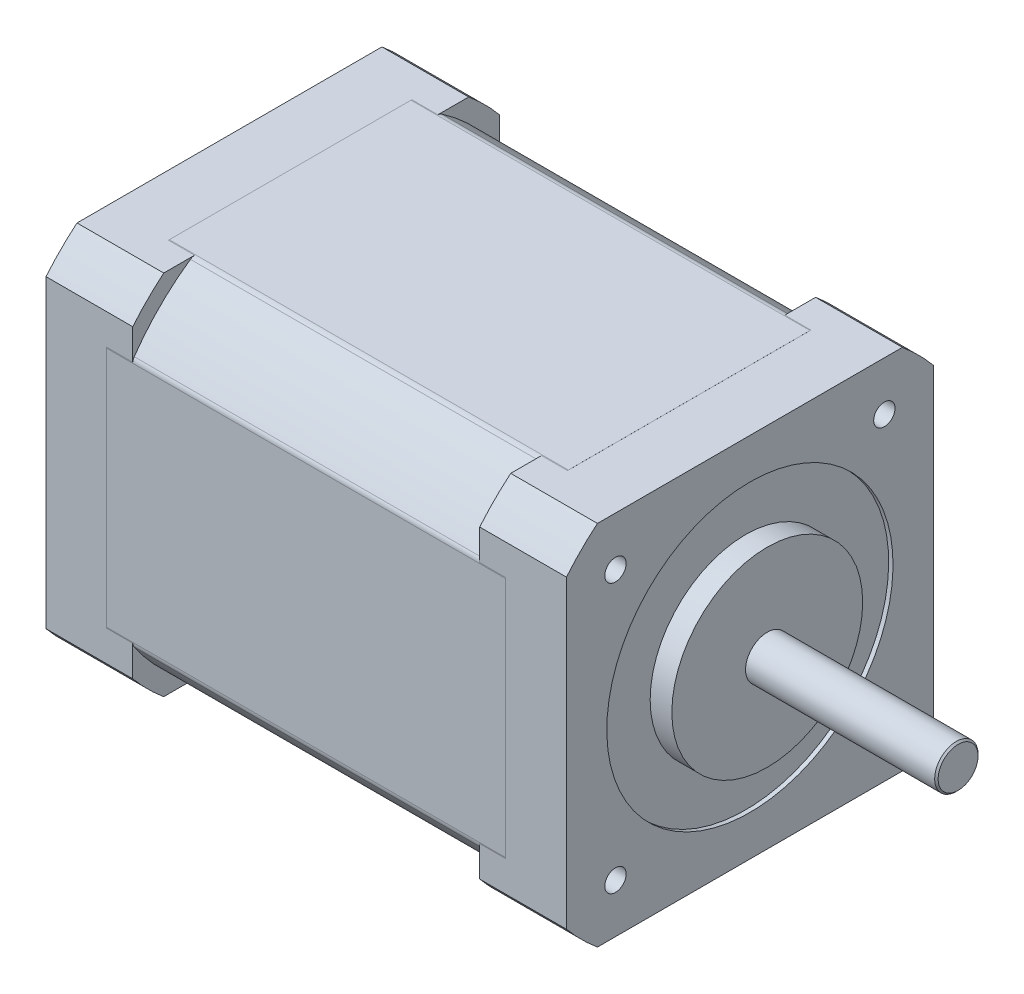
SolidWorks part; units mm, degrees
note: '?' marks a value the reader was unsure of.
ref_plane "Front Plane" through (0, 0, 0) normal (0, 0, 1) x (1, 0, 0)
ref_plane "Top Plane" through (0, 0, 0) normal (0, 1, 0) x (1, 0, 0)
ref_plane "Right Plane" through (0, 0, 0) normal (1, 0, 0) x (0, 0, -1)
ref_axis "Axis_X" through (-52.65, 0, 0) along (1, 0, 0)
ref_axis "Axis_Y" through (0, 24.8602, 0) along (0, -1, 0)?
ref_axis "Axis_Z" through (0, 0, -23.2705) along (0, 0, 1)?
sketch "Sketch1" plane through (0, 0, 0) normal (1, 0, 0) x (0, 0, -1)
  line L1 (-17.5763, 21.15) -> (17.5763, 21.15)
  line L2 (-21.15, 17.5763) -> (-21.15, -17.5763)
  line L3 (-17.5763, -21.15) -> (17.5763, -21.15)
  line L4 (21.15, 17.5763) -> (21.15, -17.5763)
  arc A0 (-17.5763, 21.15) -> (-21.15, 17.5763) centre (0, 0) ccw
  arc A1 (21.15, 17.5763) -> (17.5763, 21.15) centre (0, 0) ccw
  arc A2 (17.5763, -21.15) -> (21.15, -17.5763) centre (0, 0) ccw
  arc A3 (-21.15, -17.5763) -> (-17.5763, -21.15) centre (0, 0) ccw
  dimension "FIX_2" = 55
  dimension "FIX_1" = 42.3
extrude "Boss-Extrude1" add sketch "Sketch1" against normal blind 60
sketch "Sketch2" plane through (0, 0, 0) normal (0, 0, 1) x (1, 0, 0)
  line L0 (0, 0) -> (24, 0) construction
  line L1 (23.8, 2.5) -> (24, 2.3)
  line L2 (0, 0) -> (24, 0)
  line L3 (0, 0) -> (0, 11)
  line L4 (0, 11) -> (2, 11)
  line L5 (2, 2.5) -> (2, 11)
  line L6 (2, 2.5) -> (23.8, 2.5)
  line L9 (24, 2.3) -> (24, 0)
  dimension "FIX_3" = 22
  dimension "FIX_4" = 5
  dimension "FIX_5" = 2
  dimension "FIX_6" = 24
  dimension "FIX_7" = 45
  dimension "FIX_8" = 0.2
revolve "Revolve1" add sketch "Sketch2" angle 360 about axis through (-52.65, 0, 0) along (1, 0, 0)
ref_plane "Plane1" through (-7, 0, 0) normal (1, 0, 0) x (0, 0, -1)
ref_plane "Plane2" through (-53, 0, 0) normal (-1, 0, 0) x (0, 0, 1)
sketch "Sketch3" plane through (0, 21.15, 0) normal (0, 1, 0) x (1, 0, 0)
  line L1 (-50, 21.15) -> (-10, 21.15)
  line L2 (-50, 21.15) -> (-50, -21.15)
  line L3 (-50, -21.15) -> (-10, -21.15)
  line L4 (-10, 21.15) -> (-10, -21.15)
  line L6 (-50, 0) -> (-10, 0) construction
  line L8 (0, 17.5763) -> (0, -17.5763) construction
  line L9 (-60, 0) -> (0, 0) construction
  line L10 (-60, 17.5763) -> (-60, -17.5763) construction
  line L11 (0, -11) -> (0, 11) construction
  point P6 (-30, 0)
  dimension "FIX_12" = 42.3
  dimension "FIX_13" = 10
extrude "Cut-Extrude1" cut sketch "Sketch3" against normal through all
sketch "Sketch4" plane through (-7, 0, 0) normal (1, 0, 0) x (0, 0, -1)
  line L1 (13.9293, -21.155) -> (-13.9293, -21.155)
  line L2 (21.155, -13.9293) -> (21.155, 13.9293)
  line L3 (13.9293, 21.155) -> (-13.9293, 21.155)
  line L4 (-21.155, -13.9293) -> (-21.155, 13.9293)
  arc A0 (-20.9777, -14.4979) -> (-14.4979, -20.9777) centre (0, 0) ccw
  arc A1 (14.4979, -20.9777) -> (20.9777, -14.4979) centre (0, 0) ccw
  arc A2 (20.9777, 14.4979) -> (14.4979, 20.9777) centre (0, 0) ccw
  arc A3 (-14.4979, 20.9777) -> (-20.9777, 14.4979) centre (0, 0) ccw
  arc A4 (13.9293, 21.155) -> (14.4979, 20.9777) centre (13.9293, 20.155) cw
  arc A5 (21.155, -13.9293) -> (20.9777, -14.4979) centre (20.155, -13.9293) cw
  arc A6 (-13.9293, -21.155) -> (-14.4979, -20.9777) centre (-13.9293, -20.155) cw
  arc A7 (-21.155, 13.9293) -> (-20.9777, 14.4979) centre (-20.155, 13.9293) cw
  arc A8 (-13.9293, 21.155) -> (-14.4979, 20.9777) centre (-13.9293, 20.155) ccw
  arc A9 (14.4979, -20.9777) -> (13.9293, -21.155) centre (13.9293, -20.155) cw
  arc A10 (20.9777, 14.4979) -> (21.155, 13.9293) centre (20.155, 13.9293) cw
  arc A11 (-20.9777, -14.4979) -> (-21.155, -13.9293) centre (-20.155, -13.9293) cw
  point P20 (-14.2378, 21.155)
  dimension "FIX_14" = 51
  dimension "FIX_16" = 1
  dimension "FIX_15" = 42.31
extrude "Boss-Extrude2" add sketch "Sketch4" against normal up to surface (46 mm away) up to plane "Plane2"
sketch "Sketch5" plane through (-60, 0, 0) normal (-1, 0, 0) x (0, 0, 1)
  line L0 (0, 21.15) -> (0, -21.15) construction
  line L1 (-17.5763, 21.15) -> (17.5763, 21.15) construction
  line L2 (17.5763, -21.15) -> (-17.5763, -21.15) construction
  line L3 (-21.15, 0) -> (21.15, 0) construction
  line L4 (-21.15, -17.5763) -> (-21.15, 17.5763) construction
  line L5 (21.15, 17.5763) -> (21.15, -17.5763) construction
  circle A0 centre (-16.15, 16.15) radius 3
  circle A1 centre (16.15, 16.15) radius 3
  circle A2 centre (16.15, -16.15) radius 3
  circle A3 centre (-16.15, -16.15) radius 3
  dimension "FIX_19" = 6
  dimension "FIX_17" = 5
  dimension "FIX_18" = 5
extrude "Cut-Extrude2" cut sketch "Sketch5" against normal blind 2
ref_plane "Plane3" through (0, 0, -16.15) normal (0, 0, -1) x (-1, 0, 0)
sketch "Sketch6" plane through (0, 0, -16.15) normal (0, 0, -1) x (-1, 0, 0)
  line L0 (58, 16.15) -> (60, 16.15) construction
  line L1 (58, 16.15) -> (60, 16.15)
  line L2 (58, 16.15) -> (58, 13.4)
  line L3 (58, 13.4) -> (58.8, 13.4)
  line L4 (60, 16.15) -> (60, 14.6)
  line L5 (58, 13.15) -> (58, 19.15) construction
  line L6 (60, 13.15) -> (60, 19.15) construction
  arc A0 (60, 14.6) -> (58.8, 13.4) centre (58.8, 14.6) cw
  dimension "FIX_24" = 1.2
  dimension "FIX_23" = 5.5
  dimension "FIX_22" = 2
revolve "Revolve2" add sketch "Sketch6" angle 360 about L0
sketch "Sketch7" plane through (-60, 0, 0) normal (-1, 0, 0) x (0, 0, 1)
  line L0 (-15.7, 16.4) -> (-14.4, 16.4)
  line L1 (-17.9, 16.4) -> (-16.6, 16.4)
  line L2 (-17.9, 16.4) -> (-17.9, 15.9)
  line L3 (-17.9, 15.9) -> (-16.6, 15.9)
  line L4 (-14.4, 16.4) -> (-14.4, 15.9)
  line L5 (-17.9, 16.4) -> (-14.4, 15.9) construction
  line L6 (-17.9, 15.9) -> (-14.4, 16.4) construction
  line L7 (-16.4, 17.9) -> (-15.9, 17.9)
  line L8 (-16.4, 17.9) -> (-16.4, 16.6)
  line L9 (-16.4, 14.4) -> (-15.9, 14.4)
  line L10 (-15.9, 17.9) -> (-15.9, 16.6)
  line L11 (-16.4, 17.9) -> (-15.9, 14.4) construction
  line L12 (-16.4, 14.4) -> (-15.9, 17.9) construction
  line L13 (-16.4, 15.7) -> (-16.4, 14.4)
  line L14 (-15.7, 15.9) -> (-14.4, 15.9)
  line L15 (-15.9, 15.7) -> (-15.9, 14.4)
  circle A0 centre (-16.15, 16.15) radius 2.75 construction
  arc A1 (-16.6, 15.9) -> (-16.4, 15.7) centre (-16.6, 15.7) cw
  arc A2 (-15.9, 15.7) -> (-15.7, 15.9) centre (-15.7, 15.7) cw
  arc A3 (-15.7, 16.4) -> (-15.9, 16.6) centre (-15.7, 16.6) cw
  arc A4 (-16.4, 16.6) -> (-16.6, 16.4) centre (-16.6, 16.6) cw
  point P0 (-16.15, 16.15)
  point P5 (-16.15, 16.15)
  point P20 (-15.9, 15.9)
  dimension "FIX_29" = 0.2
  dimension "FIX_26" = 3.5
  dimension "FIX_27" = 3.5
  dimension "FIX_28" = 0.5
extrude "Cut-Extrude3" cut sketch "Sketch7" against normal blind 1.5
pattern_linear "LPattern1" count 2 spacing 32.2 along (0, -1, 0) count 2 spacing 32.2 along (0, 0, 1) of "Cut-Extrude3", "Revolve2"
hole_wizard "Tap1" positions "Sketch8" profile "Sketch9" hole size "M3x0.5" standard "JIS"
sketch "Sketch8" plane through (0, 0, 0) normal (1, 0, 0) x (0, 0, -1)
  line L1 (-15.5, 15.5) -> (15.5, -15.5) construction
  line L3 (-15.5, -15.5) -> (15.5, 15.5) construction
  point P0 (-15.5, 15.5)
  point P2 (15.5, 15.5)
  point P4 (15.5, -15.5)
  point P6 (-15.5, -15.5)
  dimension "FIX_42" = 31
  dimension "FIX_43" = 31
sketch "Sketch9" plane through (0, 15.5, 15.5) normal (0, 1, 0) x (0, 0, -1)
  line L0 (0, 0) -> (0, 5.2388)
  line L1 (0, 5.2388) -> (1.2295, 4.5)
  line L2 (1.2295, 4.5) -> (1.2295, 0)
  line L5 (1.2295, 0) -> (0, 0)
  line L10 (0, 5.2388) -> (-1.2295, 4.5) construction
  line L11 (0, 0) -> (0, 5.2388) construction
  dimension "FIX_39" = 2.459
  dimension "FIX_40" = 4.5
  dimension "FIX_41" = 118
cosmetic thread "Thread1" parameters "FIX_38"=3
cosmetic thread "Thread2" parameters "FIX_37"=3
cosmetic thread "Thread3" parameters "FIX_36"=3
cosmetic thread "Thread4" parameters "FIX_35"=3
sketch "Sketch10" plane through (0, 0, 0) normal (0, 0, 1) x (1, 0, 0)
  line L0 (0, 16.5) -> (0, 11)
  line L1 (0, 0) -> (-0.5, 0) construction
  line L3 (0, 11) -> (-0.5, 11)
  line L5 (0, 16.5) -> (-0.5, 16.5)
  line L6 (-0.5, 11) -> (-0.5, 16.5)
  dimension "FIX_44" = 0.5
  dimension "FIX_45" = 33
revolve "Cut-Revolve1" cut sketch "Sketch10" angle 360 about L1
sketch "Sketch11" plane through (0, -21.15, 0) normal (0, -1, 0) x (1, 0, 0)
  line L1 (-58, 3.25) -> (-54, 3.25)
  line L2 (-58, 3.25) -> (-58, -3.25)
  line L3 (-58, -3.25) -> (-54, -3.25)
  line L4 (-54, 3.25) -> (-54, -3.25)
  line L5 (0, 0) -> (-54, 0) construction
  line L6 (0, 17.5763) -> (0, -17.5763) construction
  line L7 (-60, 17.5763) -> (-60, -17.5763) construction
  dimension "FIX_47" = 4
  dimension "FIX_48" = 6.5
  dimension "FIX_49" = 2
extrude "Boss-Extrude3" add sketch "Sketch11" along normal blind 1.8
sketch "Sketch12" plane through (0, -22.95, 0) normal (0, -1, 0) x (1, 0, 0)
  line L2 (-56, 1.95) -> (-56, 3.25) construction
  line L3 (-54, 3.25) -> (-58, 3.25) construction
  circle A0 centre (-56, 1.95) radius 0.2
  circle A1 centre (-56, 0.65) radius 0.2
  circle A2 centre (-56, -0.65) radius 0.2
  circle A3 centre (-56, -1.95) radius 0.2
  dimension "FIX_51" = 0.4
  dimension "FIX_52" = 1.3
  dimension "FIX_53" = 1.3
  dimension "FIX_54" = 1.3
  dimension "FIX_55" = 1.3
equation "\"Factor\"= 1.082532"
